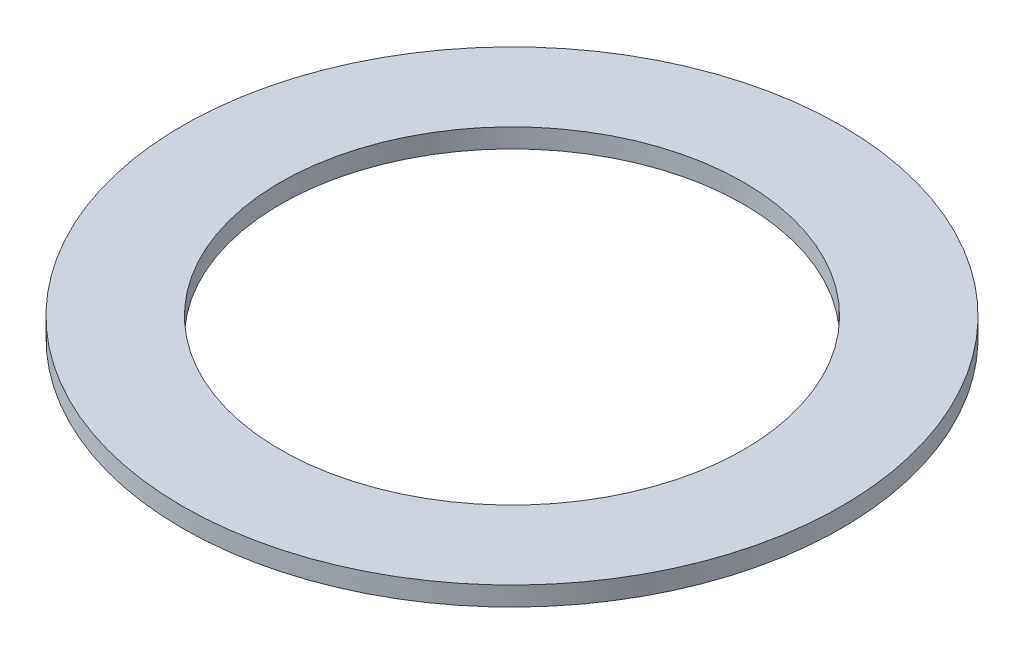
SolidWorks part; units mm, degrees
material "HDPE"
ref_plane "Piano frontale" through (0, 0, 0) normal (0, 0, 1) x (1, 0, 0)
ref_plane "Piano superiore" through (0, 0, 0) normal (0, 1, 0) x (1, 0, 0)
ref_plane "Piano destro" through (0, 0, 0) normal (1, 0, 0) x (0, 0, -1)
sketch "Schizzo1" plane through (0, 0, 0) normal (0, 0, 1) x (1, 0, 0)
  line L0 (-69, 4) -> (-48.5, 4)
  line L1 (-48.5, 4) -> (-48.5, 0)
  line L2 (-48.5, 0) -> (-69, 0)
  line L3 (-69, 0) -> (-69, 4)
  line L4 (0, 0) -> (0, 44.9066) construction
  dimension "D1" = 138
  dimension "D2" = 97
  dimension "D3" = 4
revolve "Rivoluzione1" add sketch "Schizzo1" angle 360 about L4
